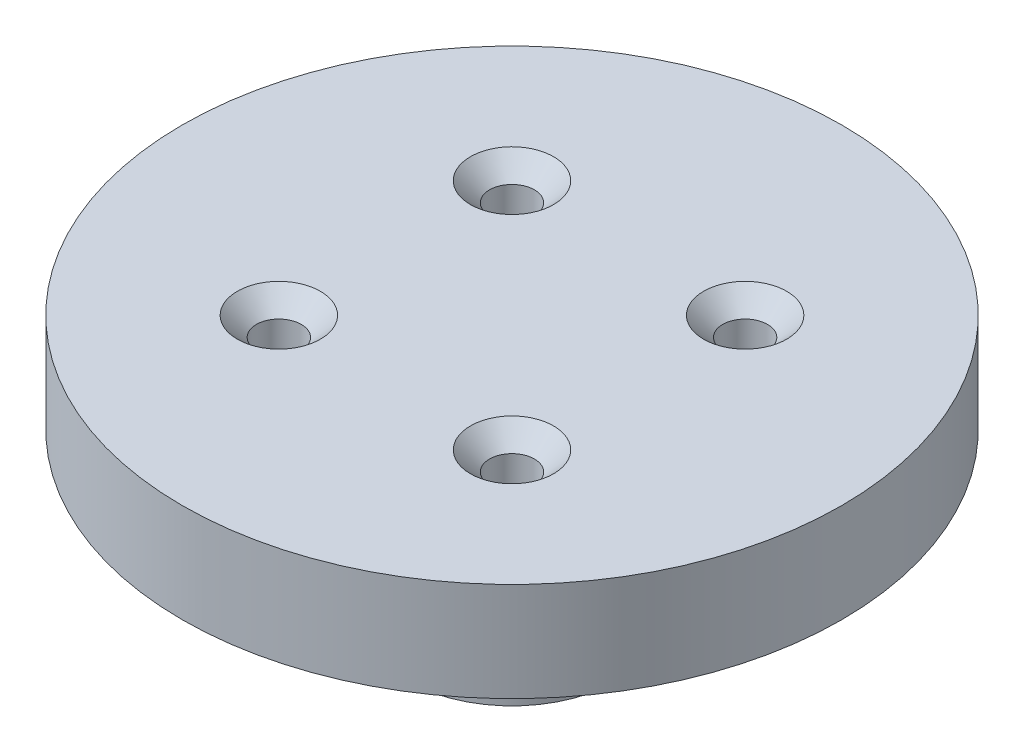
SolidWorks part; units mm, degrees
ref_plane "Front Plane" through (0, 0, 0) normal (0, 0, 1) x (1, 0, 0)
ref_plane "Top Plane" through (0, 0, 0) normal (0, 1, 0) x (1, 0, 0)
ref_plane "Right Plane" through (0, 0, 0) normal (1, 0, 0) x (0, 0, -1)
sketch "Sketch1" plane through (0, 0, 0) normal (0, 1, 0) x (1, 0, 0)
  line L1 (-25, -25) -> (25, -25)
  line L2 (-25, -25) -> (-25, 25)
  line L3 (-25, 25) -> (25, 25)
  line L4 (25, -25) -> (25, 25)
  line L5 (-25, -25) -> (25, 25) construction
  line L6 (-25, 25) -> (25, -25) construction
  circle A0 centre (0, 0) radius 25
  circle A1 centre (0, 0) radius 5
  dimension "D1" = 50
  dimension "D2" = 10
extrude "Boss-Extrude1" add sketch "Sketch1" along normal blind 7.5 contours A0 A1 | A1 region at (-17.1777, 0, 17.1777)
sketch "Sketch2" plane through (0, 7.5, 0) normal (0, 1, 0) x (1, 0, 0)
  line L1 (-25, -25) -> (25, -25)
  line L2 (-25, -25) -> (-25, 25)
  line L3 (-25, 25) -> (25, 25)
  line L4 (25, -25) -> (25, 25)
  line L5 (-25, -25) -> (25, 25) construction
  line L6 (-25, 25) -> (25, -25) construction
  line L7 (-6.1872, 11.4905) -> (-11.4905, 6.1872) construction
  circle A0 centre (0, 0) radius 25 construction
  point P0 (0, 0)
  point P12 (-8.8388, -8.8388)
  point P15 (-8.8388, 8.8388)
  point P18 (8.8388, 8.8388)
  point P19 (8.8388, -8.8388)
  point P20 (-8.8388, -8.8388)
  dimension "D2" = 12.5
  dimension "D3" = 7.5
  dimension "D5" = 12.5
  dimension "D4" = 4
hole_wizard "CSK for M3 Flat Head Machine Screw1" positions "3DSketch2" profile "Sketch5" countersink size "M3" standard "ANSI Metric" end condition through all
sketch3d "3DSketch2"
  point P0 (-8.8388, 7.5, -8.8388)
  point P3 (8.8388, 7.5, -8.8388)
  point P6 (8.8388, 7.5, 8.8388)
  point P9 (-8.8388, 7.5, 8.8388)
sketch "Sketch5" plane through (-8.8388, 7.5, -8.8388) normal (1, 0, 0) x (0, 0, 1)
  line L0 (0, 0) -> (0, 7.5)
  line L1 (0, 7.5) -> (1.725, 7.5)
  line L2 (1.7, 7.475) -> (1.7, 1.45)
  line L3 (1.7, 1.45) -> (3.15, 0)
  line L5 (3.15, 0) -> (0, 0)
  line L6 (-1.7, 1.45) -> (-3.15, 0) construction
  line L7 (1.725, 7.5) -> (1.7, 7.475)
  line L8 (-1.725, 7.5) -> (-1.7, 7.475) construction
  line L11 (0, -6.35) -> (0, 107.95) construction
  dimension "Thru Hole Dia." = 3.4
  dimension "Thru Hole Depth" = 7.5
  dimension "Near C'Sink Dia." = 6.3
  dimension "Near C'Sink Angle" = 90
  dimension "Far C'Sink Dia." = 3.45
  dimension "Far C'Sink Angle" = 90
sketch "Sketch6" plane through (0, 0, 0) normal (0, -1, 0) x (1, 0, 0)
  line L0 (4.3301, 2.5) -> (-4.3301, 2.5)
  circle A1 centre (0, 0) radius 5
  circle A3 centre (0, 0) radius 8
  point P3 (0, 0)
  dimension "D2" = 10
  dimension "D1" = 3
  dimension "D3" = 2.5
extrude "Boss-Extrude2" add sketch "Sketch6" along normal blind 12.5 contours L0 | A3 region at (0, 0, 3.5251) region at (-7.7737, 0, 0)
sketch "Sketch7" plane through (0, 0, 0) normal (0, 0, 1) x (1, 0, 0)
  line L0 (0, 0) -> (0, -12.5)
  line L1 (-8, -12.5) -> (8, -12.5) construction
  line L2 (-8, -6.25) -> (8, -6.25)
  line L3 (8, -12.5) -> (8, 0) construction
  circle A0 centre (0, -6.25) radius 1
  circle A1 centre (0, -6.25) radius 1.9
  point P10 (0, -6.25)
  dimension "D1" = 2
  dimension "D2" = 3.8
extrude "Cut-Extrude1" cut sketch "Sketch7" along normal blind 10.5 contours A0
sketch "Sketch11" plane through (0, 0, 0) normal (0, 0, 1) x (1, 0, 0)
  line L0 (0, 0) -> (0, -12.5)
  line L1 (-8, -12.5) -> (8, -12.5) construction
  line L2 (8, -6.25) -> (-8, -6.25)
  line L3 (-8, 0) -> (-8, -12.5) construction
  circle A0 centre (0, -6.25) radius 1.9
  point P10 (0, -6.25)
  dimension "D1" = 3.8
